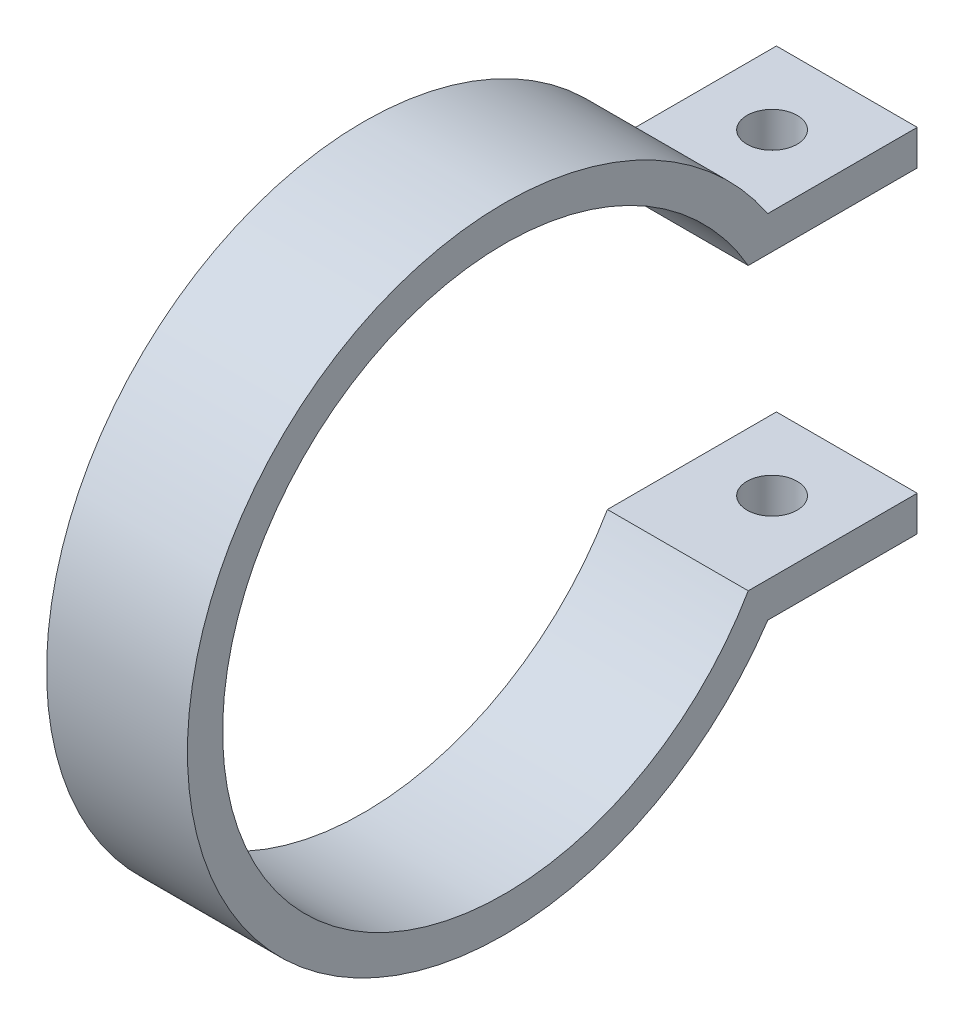
SolidWorks part; units mm, degrees
ref_plane "Front Plane" through (0, 0, 0) normal (1, 0, 0) x (0, 1, 0)
ref_plane "Top Plane" through (0, 0, 0) normal (0, 0, 1) x (0, 1, 0)
ref_plane "Right Plane" through (0, 0, 0) normal (0, 1, 0) x (-1, 0, 0)
sketch "Sketch2" plane through (0, 0, 0) normal (1, 0, 0) x (0, 1, 0)
  line L0 (-6.35, -10.9985) -> (6.35, -10.9985) construction
  line L1 (-6.35, -10.9985) -> (-6.35, -18.6185)
  line L2 (6.35, -10.9985) -> (6.35, -18.6185)
  line L3 (-7.9375, -11.8798) -> (-7.9375, -18.6185)
  line L4 (-7.9375, -18.6185) -> (-6.35, -18.6185)
  line L5 (6.35, -18.6185) -> (7.9375, -18.6185)
  line L6 (7.9375, -18.6185) -> (7.9375, -11.8798)
  arc A0 (6.35, -10.9985) -> (-6.35, -10.9985) centre (0, 0) ccw
  arc A1 (7.9375, -11.8798) -> (-7.9375, -11.8798) centre (0, 0) ccw
  point P8 (0, 0)
  point P10 (7.8641, -11.9285)
  point P12 (8.9383, -11.1787)
  dimension "D2" = 12.7
  dimension "D4" = 14.2875
  dimension "D1" = 12.7
  dimension "D3" = 7.62
  dimension "D5" = 1.5875
  dimension "D6" = 1.5875
extrude "Boss-Extrude1" add sketch "Sketch2" along normal blind 6.35
sketch "Sketch3" plane through (0, -7.9375, 0) normal (0, -1, 0) x (1, 0, 0)
  line L0 (0, -11.8798) -> (6.35, -18.6185) construction
  point P9 (3.175, -15.2491)
hole_wizard "Tap Drill for #4-40 Tap1" positions "Sketch3" profile "Sketch4" hole size "#4-40" standard "ANSI Inch" end condition through all
sketch "Sketch4" plane through (3.175, -7.9375, -15.2491) normal (1, 0, 0) x (0, 0, -1)
  line L0 (0, 0) -> (0, 22.225)
  line L1 (0, 22.225) -> (1.1303, 22.225)
  line L2 (1.1303, 22.225) -> (1.1303, 0)
  line L5 (1.1303, 0) -> (0, 0)
  line L11 (0, -6.35) -> (0, 107.95) construction
  dimension "Thru Hole Dia." = 2.2606
  dimension "Thru Hole Depth" = 22.225
